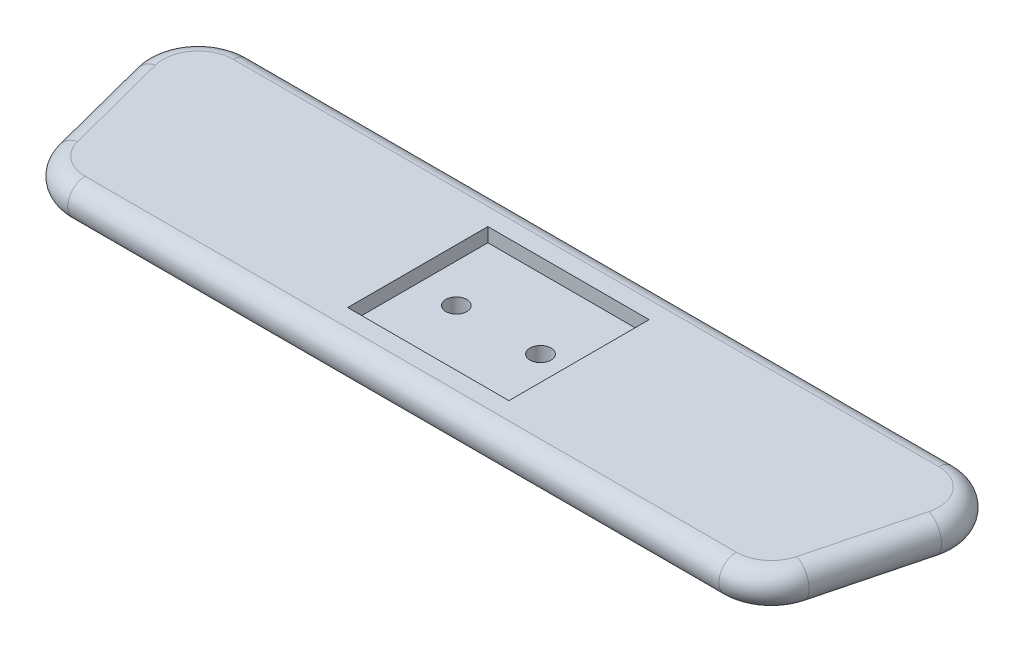
SolidWorks part; units mm, degrees
ref_plane "Front Plane" through (0, 0, 0) normal (0, 0, 1) x (1, 0, 0)
ref_plane "Top Plane" through (0, 0, 0) normal (0, 1, 0) x (1, 0, 0)
ref_plane "Right Plane" through (0, 0, 0) normal (1, 0, 0) x (0, 0, -1)
sketch "Sketch1" plane through (0, 0, 0) normal (0, 1, 0) x (1, 0, 0)
  line L0 (115.1494, 11.2443) -> (107.3909, -18.7557)
  line L1 (-100.6272, 30) -> (100.6272, 30)
  line L3 (-92.8687, -30) -> (92.8687, -30)
  line L7 (0, 0) -> (0, 19.7602) construction
  line L8 (-115.1494, 11.2443) -> (-107.3909, -18.7557)
  arc A0 (-107.3909, -18.7557) -> (-92.8687, -30) centre (-92.8687, -15) ccw
  arc A1 (107.3909, -18.7557) -> (92.8687, -30) centre (92.8687, -15) cw
  arc A2 (100.6272, 30) -> (115.1494, 11.2443) centre (100.6272, 15) cw
  arc A3 (-100.6272, 30) -> (-115.1494, 11.2443) centre (-100.6272, 15) ccw
  point P0 (0, 0)
  point P10 (-104.4829, -30)
  point P13 (104.4829, -30)
  point P16 (120, 30)
  point P19 (-120, 30)
  dimension "D2" = 15
  dimension "D1" = 240
  dimension "D3" = 75.5
extrude "Boss-Extrude1" add sketch "Sketch1" along normal blind 10 contours L1 A2 L0 A1 L3 A0 L8 A3
sketch "Sketch2" plane through (0, 10, 0) normal (0, 1, 0) x (1, 0, 0)
  line L1 (-23, 20) -> (23, 20)
  line L2 (-23, 20) -> (-23, -20)
  line L3 (-23, -20) -> (23, -20)
  line L4 (23, 20) -> (23, -20)
  line L5 (-23, 20) -> (23, -20) construction
  line L6 (-23, -20) -> (23, 20) construction
  circle A0 centre (-12, 0) radius 3
  circle A1 centre (12, 0) radius 3
  point P0 (0, 0)
  dimension "D3" = 6
  dimension "D1" = 46
  dimension "D2" = 40
  dimension "D4" = 12
  dimension "D5" = 12
extrude "Cut-Extrude1" cut sketch "Sketch2" against normal blind 4 contours L3 L4 L1 L2
extrude "Cut-Extrude2" cut sketch "Sketch2<3>" against normal through all contours A0 | A1
sketch "Sketch2<3>" plane through (0, 10, 0) normal (0, 1, 0) x (1, 0, 0) same geometry as "Sketch2"
fillet "Fillet1" 2 edges at (0, 10, 30) (0, 0, 30) type full round first side face at (0, 10, 0) second side face at (-12, 0, 3) middle face at (0, 5, 30)
sketch "Sketch3" plane through (0, 0, 0) normal (0, -1, 0) x (1, 0, 0)
  line L0 (0, 20.1575) -> (0, 0) construction
  line L1 (0, 0) -> (35.5947, 0) construction
  line L2 (92.8687, 30) -> (-92.8687, 30) construction
  circle A0 centre (-70, 8) radius 2
  circle A1 centre (-70, -8) radius 2
  circle A2 centre (70, -8) radius 2
  circle A3 centre (70, 8) radius 2
  dimension "D1" = 4
  dimension "D2" = 70
  dimension "D3" = 22
extrude "Cut-Extrude3" cut sketch "Sketch3" against normal blind 8
